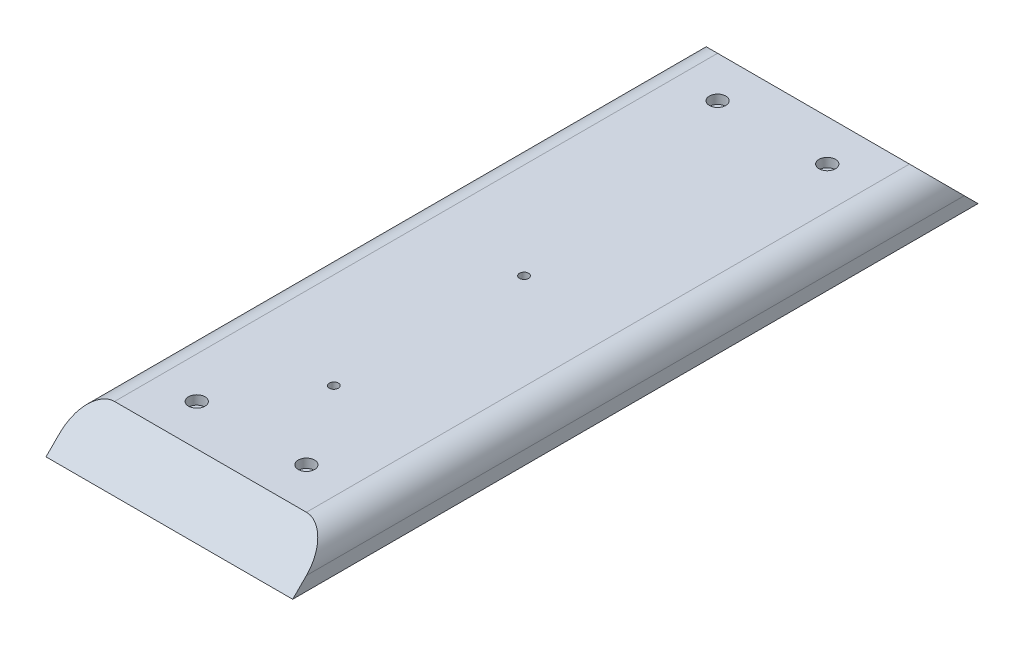
SolidWorks part; units mm, degrees
ref_plane "Front Plane" through (0, 0, 0) normal (0, 0, 1) x (1, 0, 0)
ref_plane "Top Plane" through (0, 0, 0) normal (0, 1, 0) x (1, 0, 0)
ref_plane "Right Plane" through (0, 0, 0) normal (1, 0, 0) x (0, 0, -1)
sketch "Sketch1" plane through (0, 0, 0) normal (0, 1, 0) x (1, 0, 0)
  line L1 (0, 0) -> (90, 0)
  line L2 (0, 0) -> (0, 250)
  line L3 (0, 250) -> (90, 250)
  line L4 (90, 0) -> (90, 250)
  dimension "D1" = 90
  dimension "D2" = 250
extrude "Boss-Extrude1" add sketch "Sketch1" along normal blind 15
chamfer "Chamfer1" distance 15 angle 45 2 edges at (45, 15, 0) (45, 15, -250)
fillet "Fillet1" radius 10 2 edges at (0, 15, -125) (90, 15, -125)
sketch "Sketch2" plane through (0, 15, 0) normal (0, 1, 0) x (1, 0, 0)
  line L0 (45, 0) -> (45, 30) construction
  line L1 (0, 0) -> (90, 0) construction
  line L2 (25, 30) -> (65, 30) construction
  line L3 (0, 125) -> (90, 125) construction
  line L4 (0, 5) -> (0, 245) construction
  line L5 (90, 245) -> (90, 5) construction
  circle A0 centre (25, 30) radius 1.65
  circle A1 centre (65, 30) radius 1.65
  circle A2 centre (65, 220) radius 1.65
  circle A3 centre (25, 220) radius 1.65
  point P6 (45, 30)
  dimension "D2" = 3.3
  dimension "D1" = 30
  dimension "D3" = 40
extrude "Cut-Extrude1" cut sketch "Sketch2" against normal through all
sketch "Sketch3" plane through (0, 15, 0) normal (0, 1, 0) x (1, 0, 0)
  line L0 (0, 125) -> (90, 125) construction
  line L1 (0, 5) -> (0, 245) construction
  line L2 (90, 245) -> (90, 5) construction
  circle A0 centre (25, 30) radius 3
  circle A1 centre (65, 30) radius 3
  circle A2 centre (65, 220) radius 3
  circle A3 centre (25, 220) radius 3
  dimension "D1" = 6
extrude "Cut-Extrude2" cut sketch "Sketch3" against normal blind 3.3
sketch "Sketch4" plane through (0, 15, 0) normal (0, 1, 0) x (1, 0, 0)
  line L0 (45, 0) -> (45, 250) construction
  line L1 (0, 0) -> (90, 0) construction
  line L2 (90, 250) -> (0, 250) construction
  line L3 (45, 60) -> (45, 129.4) construction
  circle A0 centre (45, 60) radius 1.65
  circle A1 centre (45, 129.4) radius 1.65
  dimension "D3" = 3.3
  dimension "D1" = 69.4
  dimension "D2" = 60
extrude "Cut-Extrude3" cut sketch "Sketch4" against normal through all
sketch "Sketch5" plane through (0, 0, 0) normal (0, -1, 0) x (1, 0, 0)
  line L1 (48.2332, -60) -> (46.6166, -57.2)
  line L2 (46.6166, -57.2) -> (43.3834, -57.2)
  line L3 (43.3834, -57.2) -> (41.7668, -60)
  line L4 (41.7668, -60) -> (43.3834, -62.8)
  line L5 (43.3834, -62.8) -> (46.6166, -62.8)
  line L6 (46.6166, -62.8) -> (48.2332, -60)
  line L7 (48.2332, -129.4) -> (46.6166, -126.6)
  line L8 (46.6166, -126.6) -> (43.3834, -126.6)
  line L9 (43.3834, -126.6) -> (41.7668, -129.4)
  line L10 (41.7668, -129.4) -> (43.3834, -132.2)
  line L11 (43.3834, -132.2) -> (46.6166, -132.2)
  line L12 (46.6166, -132.2) -> (48.2332, -129.4)
  circle A0 centre (45, -60) radius 2.8 construction
  circle A1 centre (45, -129.4) radius 2.8 construction
  dimension "D1" = 5.6
  dimension "D2" = 5.6
extrude "Cut-Extrude5" cut sketch "Sketch5" against normal blind 10
